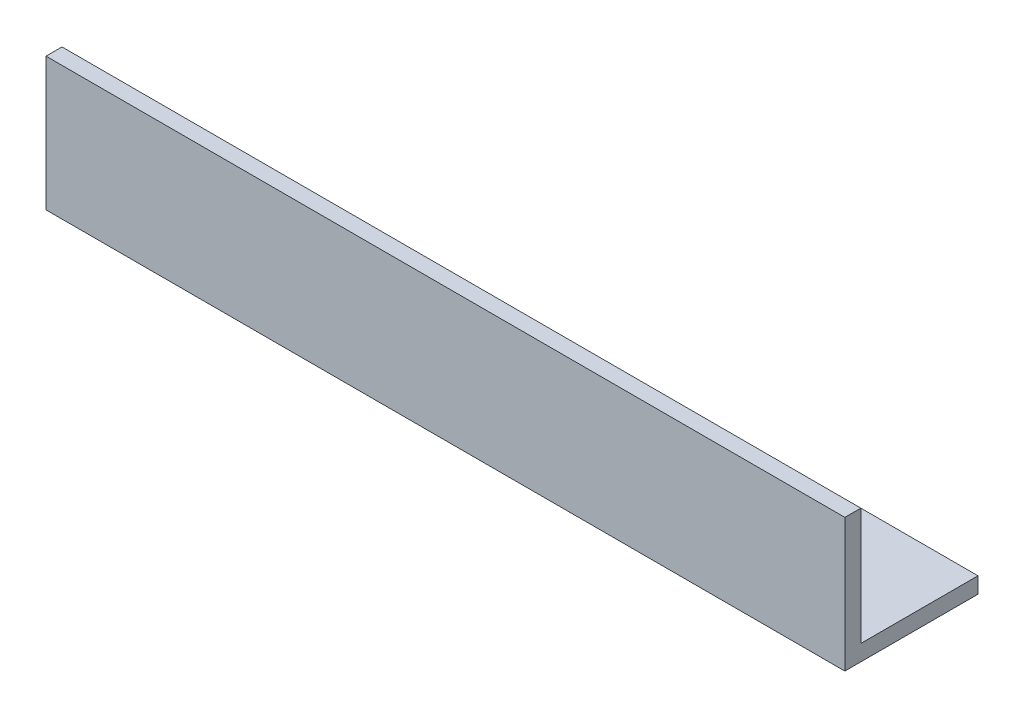
SolidWorks part; units mm, degrees
ref_plane "Спереди" through (0, 0, 0) normal (0, 0, 1) x (1, 0, 0)
ref_plane "Сверху" through (0, 0, 0) normal (0, 1, 0) x (1, 0, 0)
ref_plane "Справа" through (0, 0, 0) normal (1, 0, 0) x (0, 0, -1)
sketch "Эскиз1" plane through (0, 0, 0) normal (1, 0, 0) x (0, 0, -1)
  line L0 (0, 50) -> (0, 0)
  line L1 (0, 0) -> (50, 0)
extrude "Вытянуть-Тонкостенный1" add sketch "Эскиз1" along normal blind 300 thin thin type one direction reverse wall 6
